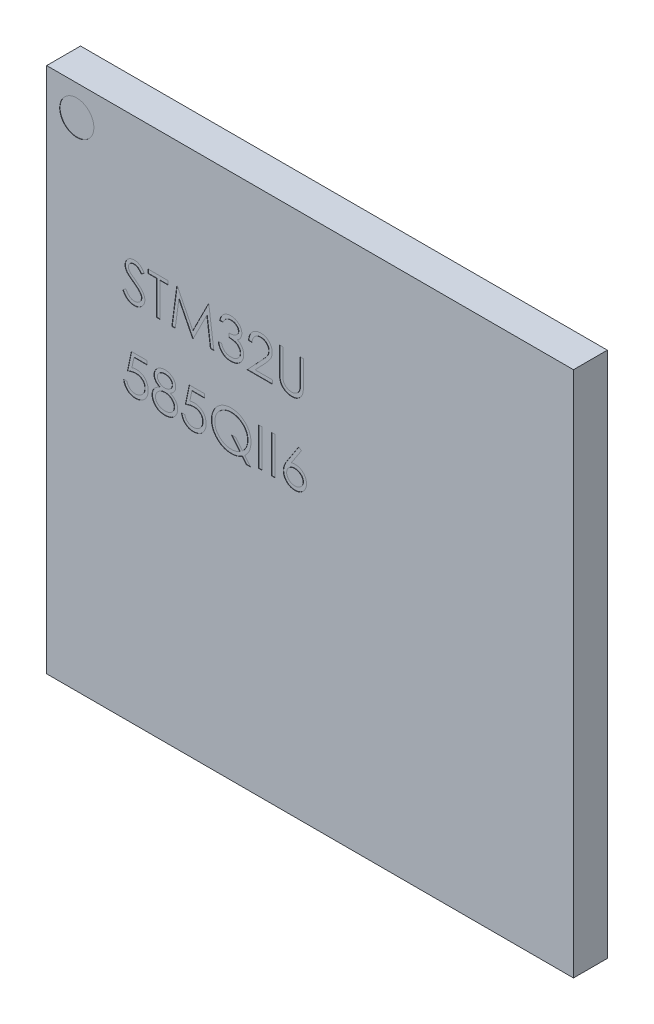
SolidWorks part; units mm, degrees
ref_plane "Front Plane" through (0, 0, 0) normal (0, 0, 1) x (1, 0, 0)
ref_plane "Top Plane" through (0, 0, 0) normal (0, 1, 0) x (1, 0, 0)
ref_plane "Right Plane" through (0, 0, 0) normal (1, 0, 0) x (0, 0, -1)
sketch "Sketch1" plane through (0, 0, 0) normal (0, 0, 1) x (1, 0, 0)
  line L0 (-2.75, 2.895) -> (-2.75, 2.605)
  line L1 (-3.5, -3.5) -> (3.5, -3.5)
  line L2 (-3.5, -3.5) -> (-3.5, 3.5)
  line L3 (-3.5, 3.5) -> (3.5, 3.5)
  line L4 (3.5, -3.5) -> (3.5, 3.5)
  line L5 (-3.5, -3.5) -> (3.5, 3.5) construction
  line L6 (-3.5, 3.5) -> (3.5, -3.5) construction
  arc A0 (-2.75, 2.895) -> (-2.75, 2.605) centre (-2.75, 2.75) ccw
  point P0 (0, 0)
  dimension "D2" = 0.75
  dimension "D4" = 0.29
  dimension "D1" = 7
  dimension "D3" = 0.75
revolve "Revolve3" add sketch "Sketch1" angle 360 about L0 region at (-2.8115, 2.75, 0)
extrude "Boss-Extrude1" add sketch "Sketch1<6>" along normal blind 0.45 contours L1 L4 L3 L2 A0 L0 | L0 A0 region at (-2.8115, 2.75, 0) region at (0.0019, -0.0019, 0)
sketch "Sketch1<6>" plane through (0, 0, 0) normal (0, 0, 1) x (1, 0, 0) same geometry as "Sketch1"
pattern_linear "LPattern1" count 12 spacing 0.5 along (1, 0, 0) of face at (-2.605, 2.75, 0)
pattern_linear "LPattern3" count 12 spacing 0.5 along (0, -1, 0) of face at (2.895, 2.75, 0) of face at (1.895, 2.75, 0) of face at (1.395, 2.75, 0) of face at (2.395, 2.75, 0) of face at (-1.605, 2.75, 0) of face at (-2.105, 2.75, 0) of face at (-2.605, 2.75, 0) of face at (-1.105, 2.75, 0)
pattern_linear "LPattern4" count 12 spacing 0.5 along (0, -1, 0) skipping (4, 0), (5, 0), (6, 0), (7, 0) of face at (0.895, 2.75, 0)
pattern_linear "LPattern5" count 12 spacing 0.5 along (0, -1, 0) skipping (4, 0), (7, 0) of face at (0.395, 2.75, 0)
pattern_linear "LPattern6" count 12 spacing 0.5 along (0, -1, 0) skipping (4, 0), (7, 0) of face at (-0.105, 2.75, 0)
pattern_linear "LPattern7" count 12 spacing 0.5 along (0, -1, 0) skipping (4, 0), (5, 0), (6, 0), (7, 0) of face at (-0.605, 2.75, 0)
sketch "Sketch2" plane through (0, 0, 0.45) normal (0, 0, 1) x (1, 0, 0)
  line L0 (-2.5031, 2.5994) -> (-2.5031, -2.0538) construction
  line L1 (-2.5031, 0.2728) -> (1.4762, 0.2728) construction
  line L7 (-3.5, 3.5) -> (3.5, 3.5) construction
  line L8 (-3.5, -3.5) -> (-3.5, 3.5) construction
  circle A0 centre (-3.1, 3.1) radius 0.2269
  text T0 "STM32U" font "Century Gothic" height 0.5
  text T1 "585QII6" font "Century Gothic" height 0.5
  dimension "D1" = 0.4
  dimension "D2" = 0.4
extrude "Cut-Extrude1" cut sketch "Sketch2" against normal blind 0.005
